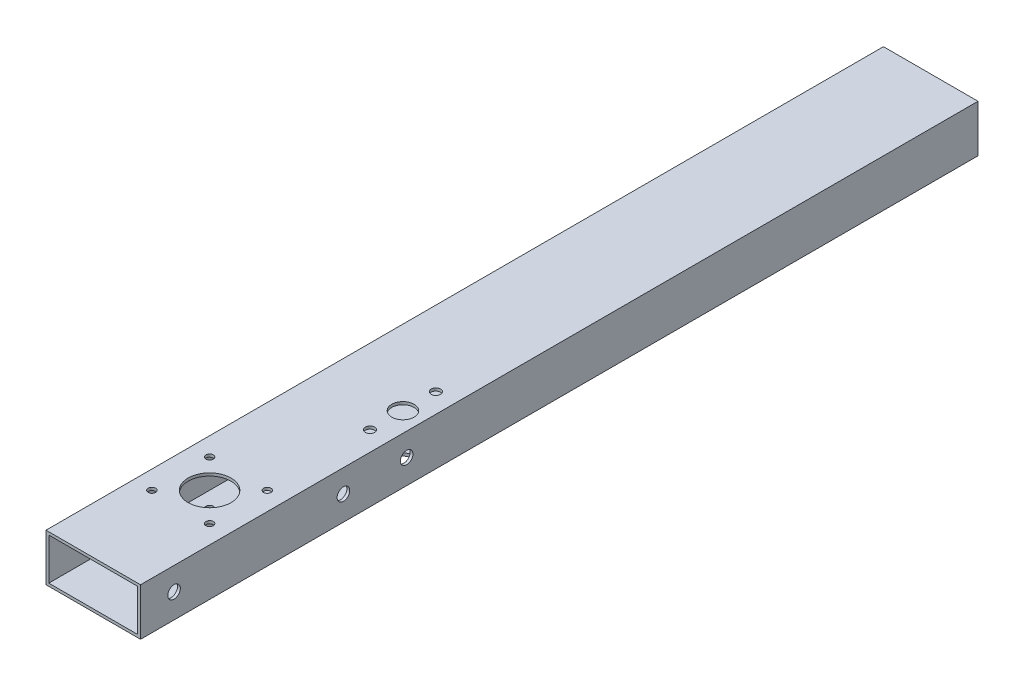
SolidWorks part; units mm, degrees
material "AISI 1015 Acero estirado en frío (SS)"
ref_plane "Alzado" through (0, 0, 0) normal (0, 0, 1) x (1, 0, 0)
ref_plane "Planta" through (0, 0, 0) normal (0, 1, 0) x (1, 0, 0)
ref_plane "Vista lateral" through (0, 0, 0) normal (1, 0, 0) x (0, 0, -1)
sketch "Croquis1" plane through (0, 0, 0) normal (0, 0, 1) x (1, 0, 0)
  line L0 (-23.9, -11.2) -> (-23.9, 11.2)
  line L1 (-25.4, -12.7) -> (25.4, -12.7)
  line L2 (-25.4, -12.7) -> (-25.4, 12.7)
  line L3 (-25.4, 12.7) -> (25.4, 12.7)
  line L4 (25.4, -12.7) -> (25.4, 12.7)
  line L5 (-25.4, -12.7) -> (25.4, 12.7) construction
  line L6 (-25.4, 12.7) -> (25.4, -12.7) construction
  line L7 (-23.9, 11.2) -> (23.9, 11.2)
  line L8 (23.9, -11.2) -> (23.9, 11.2)
  line L9 (-23.9, -11.2) -> (23.9, -11.2)
  point P0 (0, 0)
  dimension "D1" = 25.4
  dimension "D2" = 50.8
  dimension "D3" = 1.5
extrude "Saliente-Extruir1" add sketch "Croquis1" along normal blind 450
ref_plane "Plano1" through (0, -12.7, 0) normal (0, -1, 0) x (-1, 0, 0)
sketch "Croquis2" plane through (0, -12.7, 0) normal (0, -1, 0) x (-1, 0, 0)
  line L0 (0, -450) -> (0, -222.1085) construction
  line L1 (25.4, -450) -> (-25.4, -450) construction
  line L2 (25.4, -387.5) -> (-25.4, -387.5) construction
  line L3 (25.4, -450) -> (25.4, 0) construction
  line L4 (-25.4, -450) -> (-25.4, 0) construction
  circle A0 centre (0, -387.5) radius 11.5
  circle A1 centre (15.5, -403) radius 2
  circle A2 centre (-15.5, -403) radius 2
  circle A3 centre (-15.5, -372) radius 2
  circle A4 centre (15.5, -372) radius 2
  dimension "D3" = 23
  dimension "D4" = 4
  dimension "D1" = 62.5
  dimension "D2" = 15.5
  dimension "D5" = 15.5
extrude "Cortar-Extruir1" cut sketch "Croquis2" against normal blind 26
hole_wizard "Taladro de margen para 1/41" positions "Croquis3" profile "Croquis4" hole size "1/4" standard "Ansi Inch" end condition through all
sketch "Croquis3" plane through (-25.4, 197.8886, 162.9891) normal (-1, 0, 0) x (0, -1, 0)
  point P0 (197.4886, 269.0109)
  point P3 (197.4886, 178.0109)
  point P6 (197.4886, 144.0109)
  point P9 (572.8886, 144.0109)
  point P12 (572.8886, 178.0109)
  point P15 (572.8886, 269.0109)
  point P19 (197.4886, 269.0109)
  point P21 (197.4886, 144.0109)
sketch "Croquis4" plane through (-25.4, 0.4, 432) normal (0, 1, 0) x (0, 0, 1)
  line L0 (0, 0) -> (0, 50.8)
  line L1 (0, 50.8) -> (3.3782, 50.8)
  line L2 (3.3782, 50.8) -> (3.3782, 0)
  line L3 (3.3782, 0) -> (0, 0)
  line L4 (0, -6.35) -> (0, 107.95) construction
  dimension "Diámetro de taladro hasta el siguiente" = 6.7564
  dimension "Profundidad de taladro hasta el siguiente" = 50.8
sketch "Croquis5" plane through (0, -12.7, 0) normal (0, -1, 0) x (1, 0, 0)
  line L0 (-25.4, 298.5) -> (25.4, 298.5) construction
  line L1 (-25.4, 450) -> (-25.4, 0) construction
  line L2 (25.4, 450) -> (25.4, 0) construction
  line L3 (14.9, 280.8) -> (14.9, 316.2) construction
  circle A0 centre (14.9, 298.5) radius 6
  circle A1 centre (14.9, 316.2) radius 2.5
  circle A2 centre (14.9, 280.8) radius 2.5
  point P6 (0, 387.5)
  point P11 (14.9, 298.5)
  dimension "D2" = 12
  dimension "D5" = 5
  dimension "D1" = 89
  dimension "D3" = 35.4
  dimension "D4" = 10.5
extrude "Cortar-Extruir2" cut sketch "Croquis5" against normal up to surface (25.4 mm away) up to face at (-15.5, 12.7, 370)
